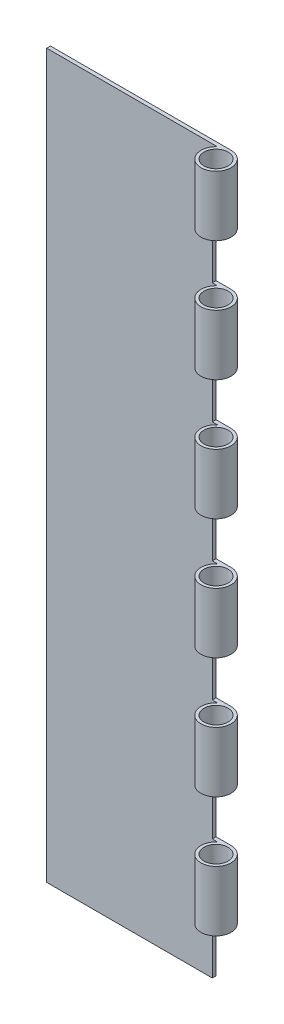
SolidWorks part; units mm, degrees
ref_plane "Front Plane" through (0, 0, 0) normal (0, 0, 1) x (1, 0, 0)
ref_plane "Top Plane" through (0, 0, 0) normal (0, 1, 0) x (1, 0, 0)
ref_plane "Right Plane" through (0, 0, 0) normal (1, 0, 0) x (0, 0, -1)
sketch "Sketch1" plane through (0, 0, 0) normal (0, 0, 1) x (1, 0, 0)
  line L1 (-130.4406, 167.7868) -> (-54.2406, 167.7868)
  line L2 (-130.4406, 167.7868) -> (-130.4406, -137.0132)
  line L3 (-130.4406, -137.0132) -> (-54.2406, -137.0132)
  line L4 (-54.2406, 167.7868) -> (-54.2406, -137.0132)
  dimension "D1" = 304.8
  dimension "D2" = 76.2
extrude "Boss-Extrude1" add sketch "Sketch1" along normal blind 1.5875
sketch "Sketch2" plane through (0, 167.7868, 0) normal (0, 1, 0) x (1, 0, 0)
  line L0 (-54.2406, 0) -> (-130.4406, 0) construction
  line L1 (-54.2406, -1.5875) -> (-54.2406, 0) construction
  circle A0 centre (-54.2406, -6.35) radius 6.35
extrude "Boss-Extrude2" add sketch "Sketch2" against normal up to surface (304.8 mm away) up to face at (-92.3406, -137.0132, 0.7937)
sketch "Sketch3" plane through (0, 0, 1.5875) normal (0, 0, 1) x (1, 0, 0)
  line L0 (-60.5906, -111.6132) -> (-60.5906, -86.2132) construction
  line L1 (-60.5906, 142.3868) -> (-38.3571, 142.3868)
  line L2 (-60.5906, 142.3868) -> (-60.5906, 116.9868)
  line L3 (-60.5906, 116.9868) -> (-38.3571, 116.9868)
  line L4 (-38.3571, 142.3868) -> (-38.3571, 116.9868)
  line L5 (-60.5906, 91.5868) -> (-38.3571, 91.5868)
  line L6 (-60.5906, 91.5868) -> (-60.5906, 66.1868)
  line L7 (-60.5906, 66.1868) -> (-38.3571, 66.1868)
  line L8 (-38.3571, 91.5868) -> (-38.3571, 66.1868)
  line L9 (-60.5906, 40.7868) -> (-38.3571, 40.7868)
  line L10 (-60.5906, 40.7868) -> (-60.5906, 15.3868)
  line L11 (-60.5906, 15.3868) -> (-38.3571, 15.3868)
  line L12 (-38.3571, 40.7868) -> (-38.3571, 15.3868)
  line L13 (-60.5906, -10.0132) -> (-38.3571, -10.0132)
  line L14 (-60.5906, -10.0132) -> (-60.5906, -35.4132)
  line L15 (-60.5906, -35.4132) -> (-38.3571, -35.4132)
  line L16 (-38.3571, -10.0132) -> (-38.3571, -35.4132)
  line L17 (-60.5906, -60.8132) -> (-35.4206, -60.8132)
  line L18 (-60.5906, -60.8132) -> (-60.5906, -86.2132)
  line L19 (-60.5906, -86.2132) -> (-35.4206, -86.2132)
  line L20 (-35.4206, -60.8132) -> (-35.4206, -86.2132)
  line L21 (-60.5906, -111.6132) -> (-40.4137, -111.6132)
  line L22 (-60.5906, -111.6132) -> (-60.5906, -137.0132)
  line L23 (-60.5906, -137.0132) -> (-40.4137, -137.0132)
  line L24 (-40.4137, -111.6132) -> (-40.4137, -137.0132)
  line L25 (-60.5906, -60.8132) -> (-60.5906, -35.4132) construction
  line L26 (-60.5906, -10.0132) -> (-60.5906, 15.3868) construction
  line L27 (-60.5906, 40.7868) -> (-60.5906, 66.1868) construction
  line L28 (-60.5906, 91.5868) -> (-60.5906, 116.9868) construction
  line L29 (-60.5906, 142.3868) -> (-60.5906, 167.7868) construction
  line L30 (-58.4407, 167.7868) -> (-130.4406, 167.7868) construction
  line L31 (-130.4406, -137.0132) -> (-58.4407, -137.0132) construction
  line L32 (-60.5906, 167.7868) -> (-60.5906, -137.0132) construction
extrude "Cut-Extrude1" cut sketch "Sketch3" against normal blind 72.4535 and the other way blind 72.4535
sketch "Sketch4" plane through (0, 167.7868, 0) normal (0, 1, 0) x (1, 0, 0)
  circle A0 centre (-54.2406, -6.35) radius 5.08
  arc A1 (-58.4407, -1.5875) -> (-54.2406, 0) centre (-54.2406, -6.35) ccw construction
extrude "Cut-Extrude2" cut sketch "Sketch4" against normal through all
